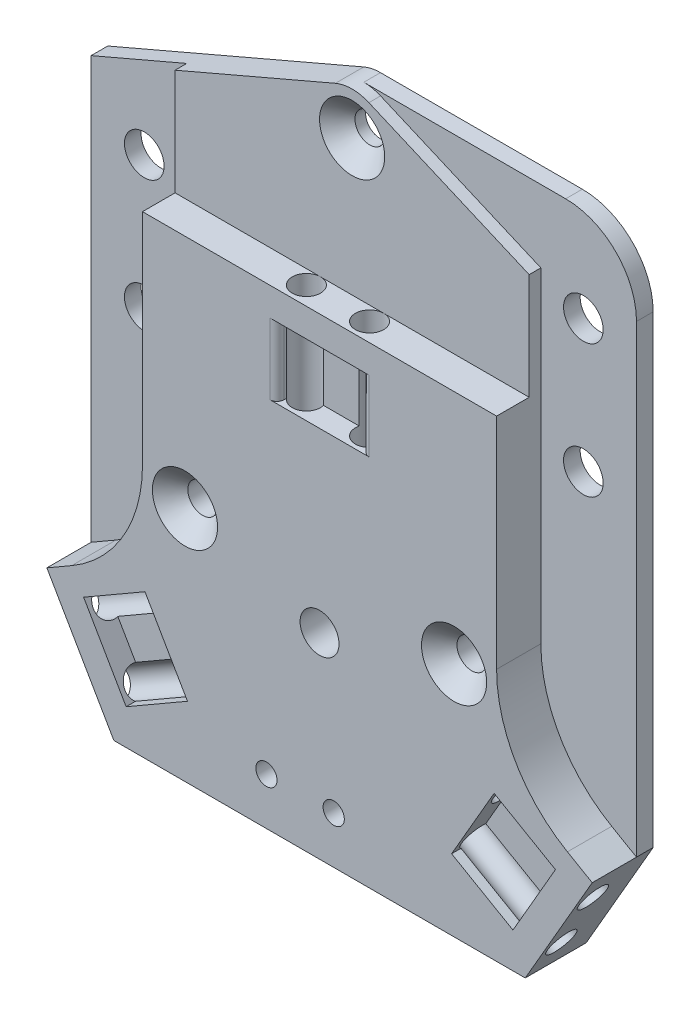
SolidWorks part; units mm, degrees
other "carriage coupler plate"
material "PET"
ref_plane "Front" through (0, 0, 0) normal (0, 0, 1) x (1, 0, 0)
ref_plane "Top" through (0, 0, 0) normal (0, 1, 0) x (1, 0, 0)
ref_plane "Right" through (0, 0, 0) normal (1, 0, 0) x (0, 0, -1)
sketch "Sketch1" plane through (0, 0, 0) normal (0, 0, 1) x (1, 0, 0)
  line L0 (0, 0) -> (0, 30) construction
  line L1 (0, 0) -> (25.9808, -15) construction
  line L2 (0, 0) -> (-25.9808, -15) construction
  dimension "D1" = 120
  dimension "D2" = 120
  dimension "D3" = 30
ref_plane "Plane1" through (0, 30, 0) normal (0, 1, 0) x (1, 0, 0)
sketch "Sketch2" plane through (0, 30, 0) normal (0, 1, 0) x (1, 0, 0)
  line L0 (-4.4589, 0) -> (0, -4.0148) construction
  line L1 (0, 0) -> (-25.9808, 0) construction
  line L2 (0, 0) -> (0, -4.0148) construction
  line L3 (-4.4589, 0) -> (0, 0) construction
  line L4 (0, -5.3962) -> (0, -4.0148) construction
  line L5 (0, -5.3962) -> (-4.4589, 0) construction
  line L7 (-4, -4.0148) -> (4, -4.0148) construction
  line L8 (3.9519, -3.3962) -> (-3.9519, -3.3962) construction
  line L9 (0, -0.3962) -> (0, -3.3962) construction
  line L10 (0, -4.0148) -> (0, -7.3926) construction
  circle A0 centre (-4.4589, 0) radius 2
  circle A1 centre (4.4589, 0) radius 2
  circle A2 centre (0, -4.0148) radius 4
  circle A3 centre (0, -5.3962) radius 5 construction
  circle A4 centre (0, -7.3926) radius 1.5
  dimension "D1" = 4
  dimension "D2" = 8
  dimension "D4" = 10
  dimension "D9" = 3
  dimension "D6" = 7.3926
  dimension "D8" = 8.9177
  dimension "D3" = 42
  dimension "D5" = 50.433
  dimension "D7" = 3.3962
  dimension "D10" = 0.6186
sketch "Sketch3" plane through (0, 0, 0) normal (0, 0, 1) x (1, 0, 0)
  line L0 (0, 30) -> (0, 35) construction
  line L2 (0, 35) -> (0, 39) construction
  line L3 (-25, 39) -> (25, 39)
  line L4 (25, 39) -> (25, -3.5116)
  line L5 (25, -3.5116) -> (38.5044, -11.3084)
  line L6 (0, 0) -> (0, 30) construction
  line L7 (-25, -3.5116) -> (-38.5044, -11.3084)
  line L8 (-25, 39) -> (-25, -3.5116)
  line L9 (4.4589, 30) -> (4.4589, 39) construction
  line L10 (25.9808, -15) -> (33.775, -19.5) construction
  line L11 (29.0456, -27.6916) -> (-29.0456, -27.6916)
  line L13 (0, 0) -> (25.9808, -15) construction
  line L14 (33.775, -19.5) -> (38.5044, -11.3084)
  line L15 (4.4589, 30) -> (0, 30) construction
  line L16 (4.4589, 30) -> (9.4589, 30) construction
  line L17 (-33.775, -19.5) -> (-38.5044, -11.3084)
  line L18 (33.775, -19.5) -> (29.0456, -27.6916)
  line L19 (-33.775, -19.5) -> (-29.0456, -27.6916)
  dimension "D1" = 5
  dimension "D2" = 4
  dimension "D3" = 25
  dimension "D4" = 120
  dimension "D5" = 5
  dimension "D6" = 9.4589
  dimension "D7" = 9.4589
  dimension "D8" = 9
  dimension "D9" = 9
extrude "Boss-Extrude1" add sketch "Sketch3" along normal blind 2.6 and the other way blind 6
fillet "Fillet1" radius 20 2 edges at (-25, -3.5116, -1.7) (25, -3.5116, -1.7)
sketch "Sketch4" plane through (0, 30, 0) normal (0, 1, 0) x (1, 0, 0)
  line L0 (0, -0.0148) -> (0, 0.4852) construction
  line L1 (5.1148, 0.4852) -> (-5.1148, 0.4852)
  line L2 (-5.1148, 0.4852) -> (-6, -0.4)
  line L3 (-6, -0.4) -> (-6, -2.6)
  line L4 (25, -2.6) -> (-25, -2.6) construction
  line L5 (-6, -2.6) -> (6, -2.6)
  line L7 (0, -5.3962) -> (-4.4589, 0) construction
  line L8 (-0.7342, -4.5076) -> (-0.5833, -4.3426)
  line L9 (6, -0.4) -> (6, -2.6)
  line L10 (5.1148, 0.4852) -> (6, -0.4)
  circle A7 centre (0, -4.0148) radius 4 construction
  dimension "D1" = 0.5
  dimension "D2" = 135
  dimension "D3" = 12
  dimension "D4" = 2.2
extrude "Cut-Extrude1" cut sketch "Sketch4" against normal blind 5 and the other way blind 5 contours L5 L9 L10 L1 L2 L3
sketch "Sketch5" plane through (0, 39, 0) normal (0, 1, 0) x (1, 0, 0)
  circle A0 centre (-4.4589, 0) radius 2 construction
  circle A1 centre (4.4589, 0) radius 2 construction
  circle A2 centre (-4.4589, 0) radius 2
  circle A3 centre (4.4589, 0) radius 2
extrude "Cut-Extrude2" cut sketch "Sketch5" against normal blind 20
fillet "Fillet3" radius 1 2 edges at (-6, 30, 2.6) (6, 30, 2.6)
ref_axis "Axis1" through (0, 0, -80.9) along (0, 0, 1)
pattern_circular "CirPattern1" count 3 over 360 about axis through (0, 0, -80.9) along (0, 0, 1) of "Cut-Extrude2", "Cut-Extrude1"
sketch "Sketch6" plane through (0, 0, 2.6) normal (0, 0, 1) x (1, 0, 0)
  circle A0 centre (0, 0) radius 2.75
  dimension "D1" = 5.5
extrude "Cut-Extrude3" cut sketch "Sketch6" against normal through all
sketch "Sketch7" plane through (0, 0, -6) normal (0, 0, -1) x (-1, 0, 0)
  line L2 (0, 0) -> (0, 58.2) construction
  line L3 (-25, 39) -> (25, 39) construction
  line L4 (-25, 39) -> (25, 39)
  line L5 (-25, 39) -> (-25, 54)
  line L6 (-25, 54) -> (-2.3663, 63.7137)
  line L7 (25, 39) -> (25, 54)
  line L8 (25, 54) -> (2.3663, 63.7137)
  arc A0 (2.3663, 63.7137) -> (-2.3663, 63.7137) centre (0, 58.2) ccw
  dimension "D1" = 12
  dimension "D2" = 19.2
  dimension "D3" = 15
extrude "Boss-Extrude2" add sketch "Sketch7" against normal blind 4
sketch "Sketch8" plane through (0, 0, 2.6) normal (0, 0, 1) x (1, 0, 0)
  line L0 (0, 0) -> (0, 58.2) construction
  line L1 (-19, 5.7) -> (19, 5.7) construction
  circle A0 centre (-19, 5.7) radius 2.1
  circle A1 centre (19, 5.7) radius 2.1
  circle A2 centre (0, 58.2) radius 2.1
  arc A3 (2.3663, 63.7137) -> (-2.3663, 63.7137) centre (0, 58.2) ccw construction
  point P10 (0, 5.7)
  dimension "D1" = 4.2
  dimension "D2" = 4.2
  dimension "D3" = 4.2
  dimension "D4" = 52.5
  dimension "D5" = 38
extrude "Cut-Extrude4" cut sketch "Sketch8" against normal through all
chamfer "Chamfer1" distance 2.5 angle 45 3 edges at (-16.9, 5.7, 2.6) (21.1, 5.7, 2.6) (-2.1, 58.2, -2)
sketch "Sketch9" plane through (0, 0, -6) normal (0, 0, -1) x (-1, 0, 0)
  line L0 (0, -27.6916) -> (0, -6.1064) construction
  line L1 (29.0456, -27.6916) -> (-29.0456, -27.6916) construction
  line L2 (-2, -21.0416) -> (7.5, -21.0416) construction
  circle A0 centre (7.5, -21.0416) radius 1.5
  circle A1 centre (-2, -21.0416) radius 1.5
  dimension "D4" = 3
  dimension "D5" = 3
  dimension "D1" = 6.65
  dimension "D2" = 7.5
  dimension "D3" = 9.5
extrude "Cut-Extrude5" cut sketch "Sketch9" against normal through all
sketch "Sketch10" plane through (0, 0, -6) normal (0, 0, -1) x (-1, 0, 0)
  line L0 (25, 54) -> (38.5044, 48.2043)
  line L2 (25, 8.0354) -> (25, 54)
  line L4 (38.5044, -11.3084) -> (38.5044, 48.2043)
  line L7 (38.5044, -11.3084) -> (38.5044, 22.7) construction
  line L8 (35, -9.2851) -> (38.5044, -11.3084)
  line L9 (25, 54) -> (2.3663, 63.7137) construction
  arc A2 (35, -9.2851) -> (25, 8.0354) centre (45, 8.0354) cw
extrude "Boss-Extrude3" add sketch "Sketch10" against normal blind 2.35
sketch "Sketch11" plane through (0, 0, -6) normal (0, 0, -1) x (-1, 0, 0)
  line L0 (-38.5044, -11.3084) -> (-38.5044, 64.2)
  line L2 (-38.5044, -11.3084) -> (-35, -9.2851)
  line L3 (-25, 8.0354) -> (-25, 54)
  line L7 (0, 64.2) -> (-38.5044, 64.2)
  line L8 (-25, 54) -> (-2.3663, 63.7137)
  line L9 (-2.3663, 63.7137) -> (-25, 54) construction
  arc A2 (-35, -9.2851) -> (-25, 8.0354) centre (-45, 8.0354) ccw
  arc A4 (2.3663, 63.7137) -> (-2.3663, 63.7137) centre (0, 58.2) ccw construction
  arc A5 (-2.3663, 63.7137) -> (0, 64.2) centre (0, 58.2) cw
extrude "Boss-Extrude4" add sketch "Sketch11" against normal blind 2.35
sketch "Sketch12" plane through (0, 0, -3.65) normal (0, 0, 1) x (1, 0, 0)
  line L0 (-38.5044, 39.8275) -> (-31, 39.8275) construction
  line L1 (-38.5044, -11.3084) -> (-38.5044, 48.2043) construction
  line L2 (38.5044, 50.8275) -> (31, 50.8275) construction
  line L3 (38.5044, 64.2) -> (38.5044, -11.3084) construction
  line L4 (25, 8.0354) -> (25, 54) construction
  line L5 (-25, 54) -> (-25, 8.0354) construction
  line L6 (25, 39) -> (-25, 39) construction
  line L7 (-31, 39.8275) -> (-31, 21.0775) construction
  line L8 (25, 39) -> (4.4589, 39) construction
  line L9 (31, 50.8275) -> (31, 32.0775) construction
  circle A0 centre (-31, 39.8275) radius 2.8
  circle A1 centre (31, 50.8275) radius 2.8
  circle A2 centre (-31, 21.0775) radius 2.8
  circle A3 centre (31, 32.0775) radius 2.8
  dimension "D5" = 5.6
  dimension "D6" = 5.6
  dimension "D7" = 5.6
  dimension "D9" = 5.6
  dimension "D1" = 0.8275
  dimension "D2" = 11.8275
  dimension "D3" = 6
  dimension "D4" = 6
  dimension "D8" = 18.75
  dimension "D10" = 18.75
extrude "Cut-Extrude6" cut sketch "Sketch12" against normal blind 2.35
fillet "Fillet4" radius 10 1 edges at (38.5044, 64.2, -4.825)
